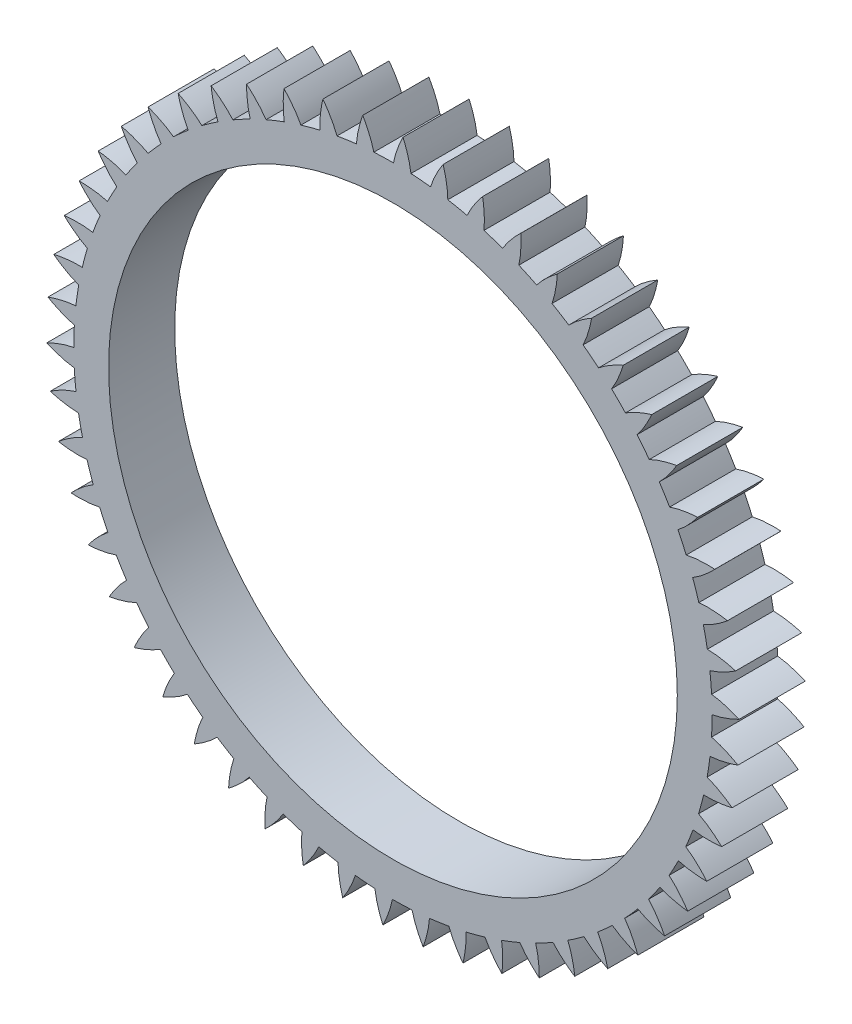
SolidWorks part; units mm, degrees
ref_plane "Front Plane" through (0, 0, 0) normal (0, 0, 1) x (1, 0, 0)
ref_plane "Top Plane" through (0, 0, 0) normal (0, 1, 0) x (1, 0, 0)
ref_plane "Right Plane" through (0, 0, 0) normal (1, 0, 0) x (0, 0, -1)
sketch "Sketch1" plane through (0, 0, 0) normal (0, 0, 1) x (1, 0, 0)
  line L0 (0, 0) -> (52.4519, -1.5262) construction
  line L1 (0, 0) -> (52.4519, 1.5262) construction
  line L2 (0, 0) -> (52.4519, -1.5262) construction
  line L3 (0, 0) -> (52.4741, 0) construction
  line L4 (0, 0) -> (52.2744, 4.5734) construction
  line L5 (0, 0) -> (52.4519, 1.5262)
  line L6 (48.237, -1.4036) -> (42.9818, -1.2506)
  circle A0 centre (0, 0) radius 50.6 construction
  circle A1 centre (0, 0) radius 48.2574 construction
  circle A2 centre (0, 0) radius 47.5484 construction
  circle A3 centre (0, 0) radius 52.4741 construction
  arc A4 (48.2533, 0.6333) -> (48.237, -1.4036) centre (0, 0) cw
  arc A5 (52.3753, 3.2182) -> (52.1207, -6.0799) centre (0, 0) cw
  arc A6 (42.9818, -1.2506) -> (42.9818, 1.2506) centre (0, 0) ccw
  spline S0 degree 4 poles (47.5484, 0) (47.6112, 0.0018) (47.7366, 0.009) (47.9743, 0.0351) (48.3224, 0.09) (48.9188, 0.2125) (49.8514, 0.4702) (51.0763, 0.915) (52.7294, 1.6795) (54.5797, 2.7428) (56.506, 4.0791) (58.4581, 5.6841) (60.2875, 7.4269) (61.9965, 9.2875) (63.6661, 11.3468) (65.5727, 14.0192) (67.5998, 17.3703) (69.6104, 21.4518) (71.4211, 26.1723) (72.8241, 31.0286) (73.8355, 35.9808) (74.3915, 40.3678) (74.6426, 44.1482) (74.7063, 47.304) (74.6718, 49.8289) (74.5535, 52.3511) (74.3534, 54.8684) (74.0032, 58.005) (73.5222, 61.1257) (72.9762, 63.9129) (72.4048, 66.3738) (72.0712, 67.6936) (71.8561, 68.5055) (71.6703, 69.1859) (71.4684, 69.9045) (71.2972, 70.4962) (70.9615, 71.62) (70.6933, 72.4658) (70.3553, 73.5115) (70.0426, 74.4282) (69.6958, 75.4214) (69.3545, 76.3545) (69.08, 77.0882) (68.9003, 77.5524) (68.8066, 77.7942) knots 0 0 0 0 0 0.002802 0.005604 0.010661 0.015718 0.02996 0.048734 0.068727 0.096889 0.125051 0.153212 0.181374 0.209535 0.237696 0.271429 0.327752 0.384075 0.440398 0.496721 0.553044 0.609367 0.637529 0.66569 0.693852 0.722013 0.750174 0.778336 0.834659 0.86282 0.876901 0.890982 0.895509 0.900036 0.909091 0.920455 0.931818 0.943182 0.954545 0.965909 0.977273 0.988636 1 1 1 1 1 construction
  spline S1 degree 4 poles (47.5484, 0) (47.6112, 0.0018) (47.7366, 0.009) (47.9743, 0.0351) (48.3224, 0.09) (48.9188, 0.2125) (49.8514, 0.4702) (51.0763, 0.915) (52.7294, 1.6795) (54.5797, 2.7428) (56.506, 4.0791) (58.4581, 5.6841) (60.2875, 7.4269) (61.9965, 9.2875) (63.6661, 11.3468) (65.5727, 14.0192) (67.5998, 17.3703) (69.6104, 21.4518) (71.4211, 26.1723) (72.8241, 31.0286) (73.8355, 35.9808) (74.3915, 40.3678) (74.6426, 44.1482) (74.7063, 47.304) (74.6718, 49.8289) (74.5535, 52.3511) (74.3534, 54.8684) (74.0032, 58.005) (73.5222, 61.1257) (72.9762, 63.9129) (72.4048, 66.3738) (72.0712, 67.6936) (71.8561, 68.5055) (71.6703, 69.1859) (71.5463, 69.6274) (71.469, 69.8988) (71.4179, 70.076) knots 0 0 0 0 0 0.002802 0.005604 0.010661 0.015718 0.02996 0.048734 0.068727 0.096889 0.125051 0.153212 0.181374 0.209535 0.237696 0.271429 0.327752 0.384075 0.440398 0.496721 0.553044 0.609367 0.637529 0.66569 0.693852 0.722013 0.750174 0.778336 0.834659 0.86282 0.876901 0.890982 0.895509 0.900036 0.909091 0.909091 0.909091 0.909091 0.909091
  dimension "pitchRadius" = 50.6
  dimension "addendumRadius" = 52.4741
  dimension "dedendumRadius" = 48.2574
  dimension "baseRadius" = 47.5484
  dimension "D1" = 3.333
  dimension "D2" = 1.667
  dimension "toothArc" = 6.667
  dimension "D3" = 43
extrude "Boss-Extrude1" add sketch "Sketch1" along normal blind 10 contours S1 A5 L5 A6 L6 A4 region at (46.4133, 0.1773, 0)
mirror "Mirror1" about plane through (0, 0, 10) normal (-0.0291, 0.9996, 0) of "Boss-Extrude1"
pattern_circular "CirPattern2" count 54 over 360 about axis through (0, 0, 10) along (0, 0, -1) of "Mirror1", "Boss-Extrude1"
ref_axis "Axis1" through (0, 0, 0) along (0, 0, 1)
equation "\"D1@Sketch1\"=\"toothArc@Sketch1\"/2"
equation "\"D2@Sketch1\"=\"toothArc@Sketch1\"/4"
equation "\"pitchRadius\"= 5.06"
equation "\"nTeeth\"= 54"
equation "\"pressureAngle\"= 20"
equation "\"baseRadius\"= \"pitchRadius\" * cos ( \"pressureAngle\" )"
equation "\"diametralPitch\"= \"nTeeth\" / ( 2 * \"pitchRadius\" )'note units: cm^-1"
equation "\"dedendum\"= 1.25 / \"diametralPitch\"'for full depth, 20 deg pressure angle"
equation "\"addendum\"= 1 / \"diametralPitch\""
equation "\"pitchRadius@Sketch1\"= \"pitchRadius\""
equation "\"addendumRadius@Sketch1\"= \"pitchRadius\" + \"addendum\""
equation "\"dedendumRadius@Sketch1\"= \"pitchRadius\" - \"dedendum\""
equation "\"baseRadius@Sketch1\"= \"baseRadius\""
equation "\"toothArc@Sketch1\"=360/\"nTeeth\""
